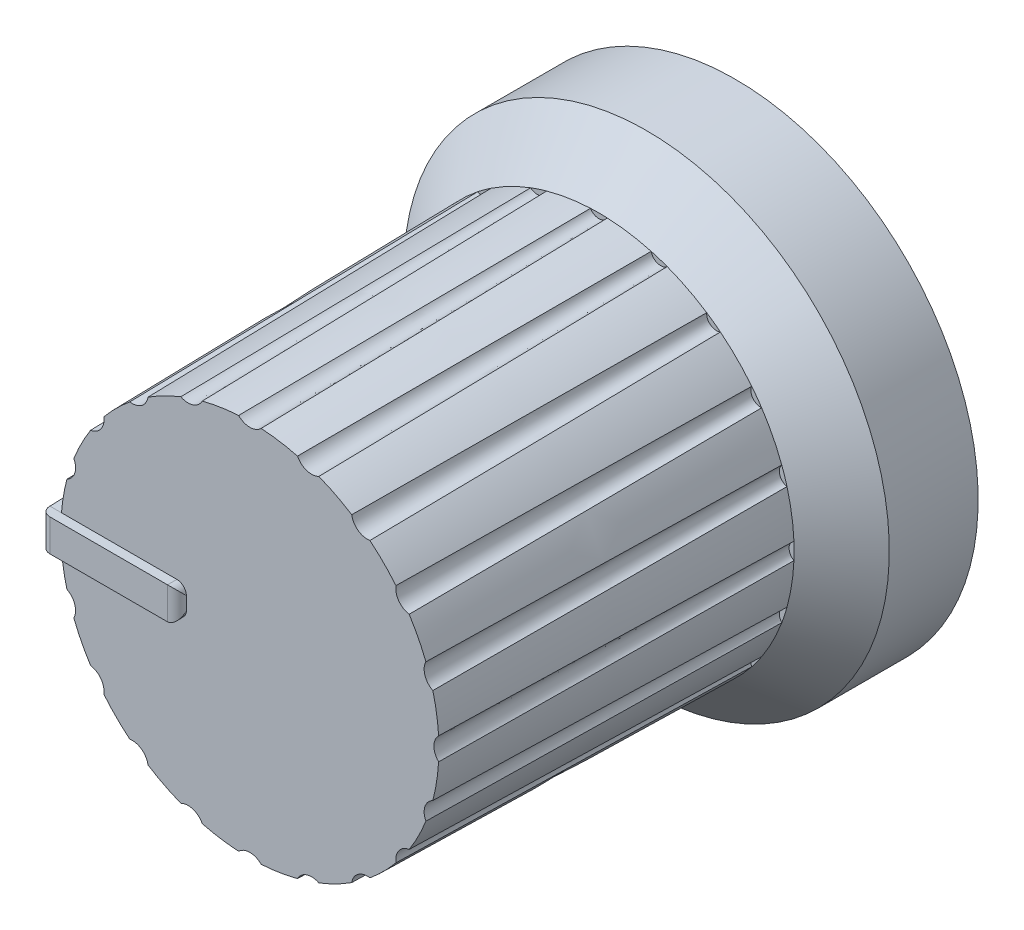
SolidWorks part; units mm, degrees
ref_plane "Front Plane" through (0, 0, 0) normal (0, 0, 1) x (1, 0, 0)
ref_plane "Top Plane" through (0, 0, 0) normal (0, 1, 0) x (1, 0, 0)
ref_plane "Right Plane" through (0, 0, 0) normal (1, 0, 0) x (0, 0, -1)
sketch "Sketch1" plane through (0, 0, 0) normal (0, 0, 1) x (1, 0, 0)
  circle A0 centre (0, 0) radius 7.65
  dimension "D1" = 15.3
extrude "Boss-Extrude1" add sketch "Sketch1" along normal blind 4.3
sketch "Sketch2" plane through (0, 0, 4.3) normal (0, 0, 1) x (1, 0, 0)
  circle A0 centre (0, 0) radius 6.15
  dimension "D1" = 12.3
extrude "Boss-Extrude2" add sketch "Sketch2" along normal blind 11 draft 1
chamfer "Chamfer1" distance 1.5 angle 45 1 edges at (7.65, 0, 4.3)
sketch "Sketch3" plane through (0, 0, 15.3) normal (0, 0, 1) x (1, 0, 0)
  circle A0 centre (0, 6.3) radius 0.5
  circle A1 centre (1.9468, 5.9917) radius 0.5
  circle A2 centre (3.703, 5.0968) radius 0.5
  circle A3 centre (5.0968, 3.703) radius 0.5
  circle A4 centre (5.9917, 1.9468) radius 0.5
  circle A5 centre (6.3, 0) radius 0.5
  circle A6 centre (5.9917, -1.9468) radius 0.5
  circle A7 centre (5.0968, -3.703) radius 0.5
  circle A8 centre (3.703, -5.0968) radius 0.5
  circle A9 centre (1.9468, -5.9917) radius 0.5
  circle A10 centre (0, -6.3) radius 0.5
  circle A11 centre (-1.9468, -5.9917) radius 0.5
  circle A12 centre (-3.703, -5.0968) radius 0.5
  circle A13 centre (-5.0968, -3.703) radius 0.5
  circle A14 centre (-5.9917, -1.9468) radius 0.5
  circle A15 centre (-6.3, 0) radius 0.5
  circle A16 centre (-5.9917, 1.9468) radius 0.5
  circle A17 centre (-5.0968, 3.703) radius 0.5
  circle A18 centre (-3.703, 5.0968) radius 0.5
  circle A19 centre (-1.9468, 5.9917) radius 0.5
  point P44 (0, 0)
  dimension "D1" = 1
  dimension "D2" = 6.3
  dimension "D3" = 20
extrude "Cut-Extrude2" cut sketch "Sketch3" against normal blind 11 draft 1
sketch "Sketch4" plane through (0, 0, 15.3) normal (0, 0, 1) x (1, 0, 0)
  line L1 (-6.3, 0.5) -> (-2, 0.5)
  line L2 (-6.3, 0.5) -> (-6.3, -0.5)
  line L3 (-6.3, -0.5) -> (-2, -0.5)
  line L4 (-2, 0.5) -> (-2, -0.5)
  dimension "D1" = 2
  dimension "D2" = 1
  dimension "D3" = 0.5
  dimension "D4" = 4.3
extrude "Boss-Extrude3" add sketch "Sketch4" against normal blind 12 draft 1 and the other way blind 0.3 draft 1 draft outward yes other way draft outward yes
fillet "Fillet1" radius 0.3 1 edges at (-6.3052, 0, 15.6)
fillet "Fillet2" radius 0.3 3 edges at (-1.9948, 0, 15.6) (-1.9974, -0.5026, 15.45) (-1.9974, 0.5026, 15.45)
sketch "Sketch5" plane through (0, 0, 0) normal (0, 0, -1) x (-1, 0, 0)
  circle A0 centre (0, 0) radius 5.9
  dimension "D1" = 11.8
extrude "Cut-Extrude3" cut sketch "Sketch5" against normal blind 3
sketch "Sketch7" plane through (0, 0, 3) normal (0, 0, -1) x (-1, 0, 0)
  circle A0 centre (0, 0) radius 3
  dimension "D1" = 6
extrude "Cut-Extrude4" cut sketch "Sketch7" against normal blind 11
